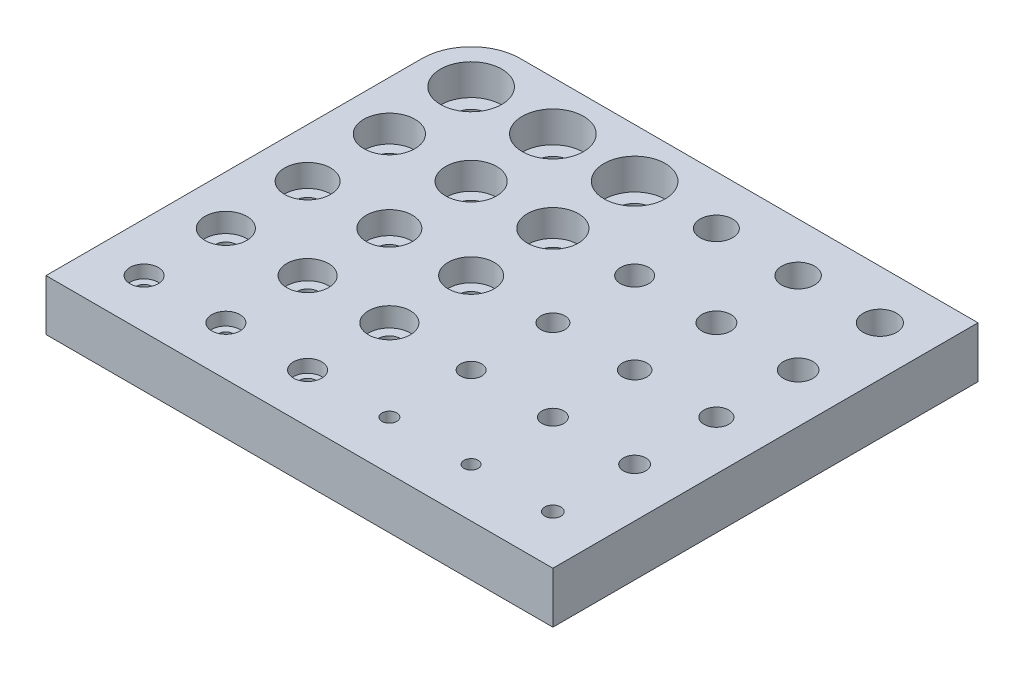
SolidWorks part; units mm, degrees
ref_plane "Front Plane" through (0, 0, 0) normal (0, 0, 1) x (1, 0, 0)
ref_plane "Top Plane" through (0, 0, 0) normal (0, 1, 0) x (1, 0, 0)
ref_plane "Right Plane" through (0, 0, 0) normal (1, 0, 0) x (0, 0, -1)
sketch "Sketch1" plane through (0, 0, 0) normal (0, 1, 0) x (1, 0, 0)
  line L0 (20.32, 7.62) -> (7.62, 7.62) construction
  line L1 (0, 0) -> (40.64, 0)
  line L2 (0, 0) -> (0, 66.04)
  line L3 (0, 66.04) -> (40.64, 66.04)
  line L4 (40.64, 0) -> (40.64, 66.04)
  line L5 (7.62, 7.62) -> (7.62, 20.32) construction
  line L6 (7.62, 7.62) -> (20.32, 7.62) construction
  circle A1 centre (20.32, 58.42) radius 2.5527
  circle A2 centre (33.02, 58.42) radius 2.5908
  circle A5 centre (33.02, 45.72) radius 2.286
  circle A6 centre (20.32, 45.72) radius 2.2479
  circle A9 centre (20.32, 33.02) radius 1.8987
  circle A10 centre (33.02, 33.02) radius 1.9304
  circle A13 centre (33.02, 20.32) radius 1.75
  circle A14 centre (20.32, 20.32) radius 1.7
  circle A16 centre (20.32, 7.62) radius 1.1
  circle A18 centre (33.02, 7.62) radius 1.25
  circle A20 centre (7.62, 58.42) radius 2.5273
  circle A21 centre (7.62, 45.72) radius 2.1971
  circle A22 centre (7.62, 33.02) radius 1.8669
  circle A23 centre (7.62, 7.62) radius 1.15
  circle A24 centre (7.62, 20.32) radius 1.65
  point P4 (7.62, 7.62)
  point P7 (20.32, 7.62)
  point P9 (33.02, 7.62)
  point P11 (20.32, 20.32)
  point P12 (33.02, 20.32)
  point P14 (20.32, 33.02)
  point P15 (33.02, 33.02)
  point P17 (20.32, 45.72)
  point P18 (33.02, 45.72)
  point P20 (20.32, 58.42)
  point P21 (33.02, 58.42)
  point P23 (7.62, 20.32)
  point P24 (7.62, 33.02)
  point P25 (7.62, 45.72)
  point P26 (7.62, 58.42)
  point P65 (7.6185, 7.62)
  dimension "D8" = 5.1054
  dimension "D9" = 5.1816
  dimension "D11" = 4.572
  dimension "D13" = 4.4958
  dimension "D14" = 3.7973
  dimension "D15" = 3.8608
  dimension "D17" = 3.4
  dimension "D18" = 3.5
  dimension "D20" = 2.2
  dimension "D21" = 2.5
  dimension "D23" = 5.0546
  dimension "D24" = 3.3
  dimension "D25" = 2.3
  dimension "D26" = 3.7338
  dimension "D27" = 4.3942
  dimension "D1" = 3
  dimension "D2" = 5
  dimension "D3" = 7.62
  dimension "D4" = 7.62
  dimension "D5" = 7.62
  dimension "D6" = 7.62
  dimension "D7" = 12.7
extrude "Boss-Extrude1" add sketch "Sketch1" against normal blind 7.9375
pattern_linear "LPattern1" count 2 spacing 38.1 along (1, 0, 0) of bodies 101
combine bodies "Combine1" operation type add bodies to combine 107 101
hole_wizard "CBORE for #10 Socket Head Cap Screw1" positions "Sketch2" profile "Sketch3" counterbore size "#10" standard "ANSI Inch" end condition through all
sketch "Sketch2" plane through (0, 0, 0) normal (0, 1, 0) x (1, 0, 0)
  point P0 (7.62, 58.42)
  point P4 (20.32, 58.42)
  point P7 (33.02, 58.42)
sketch "Sketch3" plane through (7.62, 0, -58.42) normal (1, 0, 0) x (0, 0, 1)
  line L0 (0, 0) -> (0, 7.9375)
  line L1 (0, 7.9375) -> (2.4892, 7.9375)
  line L3 (2.4892, 7.9375) -> (2.4892, 4.826)
  line L4 (2.4892, 4.826) -> (4.7625, 4.826)
  line L5 (4.7625, 4.826) -> (4.7625, 0)
  line L7 (4.7625, 0) -> (0, 0)
  line L11 (0, -6.35) -> (0, 107.95) construction
  dimension "Thru Hole Dia." = 4.9784
  dimension "Thru Hole Depth" = 7.9375
  dimension "C'Bore Dia." = 9.525
  dimension "C'Bore Depth" = 4.826
hole_wizard "CBORE for #8 Socket Head Cap Screw1" positions "Sketch4" profile "Sketch5" counterbore size "#8" standard "ANSI Inch" end condition through all
sketch "Sketch4" plane through (0, 0, 0) normal (0, 1, 0) x (1, 0, 0)
  point P0 (7.62, 45.72)
  point P3 (20.32, 45.72)
  point P6 (33.02, 45.72)
sketch "Sketch5" plane through (7.62, 0, -45.72) normal (1, 0, 0) x (0, 0, 1)
  line L0 (0, 0) -> (0, 7.9375)
  line L1 (0, 7.9375) -> (2.1526, 7.9375)
  line L3 (2.1526, 7.9375) -> (2.1526, 4.1656)
  line L4 (2.1526, 4.1656) -> (3.9687, 4.1656)
  line L5 (3.9687, 4.1656) -> (3.9687, 0)
  line L7 (3.9687, 0) -> (0, 0)
  line L11 (0, -6.35) -> (0, 107.95) construction
  dimension "Thru Hole Dia." = 4.3053
  dimension "Thru Hole Depth" = 7.9375
  dimension "C'Bore Dia." = 7.9375
  dimension "C'Bore Depth" = 4.1656
hole_wizard "CBORE for #6 Socket Head Cap Screw1" positions "Sketch6" profile "Sketch7" counterbore size "#6" standard "ANSI Inch" end condition through all
sketch "Sketch6" plane through (0, 0, 0) normal (0, 1, 0) x (1, 0, 0)
  point P0 (7.62, 33.02)
  point P3 (20.32, 33.02)
  point P6 (33.02, 33.02)
sketch "Sketch7" plane through (7.62, 0, -33.02) normal (1, 0, 0) x (0, 0, 1)
  line L0 (0, 0) -> (0, 7.9375)
  line L1 (0, 7.9375) -> (1.8288, 7.9375)
  line L3 (1.8288, 7.9375) -> (1.8288, 3.5052)
  line L4 (1.8288, 3.5052) -> (3.5725, 3.5052)
  line L5 (3.5725, 3.5052) -> (3.5725, 0)
  line L7 (3.5725, 0) -> (0, 0)
  line L11 (0, -6.35) -> (0, 107.95) construction
  dimension "Thru Hole Dia." = 3.6576
  dimension "Thru Hole Depth" = 7.9375
  dimension "C'Bore Dia." = 7.145
  dimension "C'Bore Depth" = 3.5052
hole_wizard "CBORE for M3 SHCS1" positions "Sketch8" profile "Sketch9" counterbore size "M3" standard "ANSI Metric" end condition through all
sketch "Sketch8" plane through (0, 0, 0) normal (0, 1, 0) x (1, 0, 0)
  point P0 (7.62, 20.32)
  point P3 (20.32, 20.32)
  point P6 (33.02, 20.32)
  point P12 (0, 0)
sketch "Sketch9" plane through (7.62, 0, -20.32) normal (1, 0, 0) x (0, 0, 1)
  line L0 (0, 0) -> (0, 7.9375)
  line L1 (0, 7.9375) -> (1.6, 7.9375)
  line L3 (1.6, 7.9375) -> (1.6, 3)
  line L4 (1.6, 3) -> (3.25, 3)
  line L5 (3.25, 3) -> (3.25, 0)
  line L7 (3.25, 0) -> (0, 0)
  line L11 (0, -6.35) -> (0, 107.95) construction
  dimension "Thru Hole Dia." = 3.2
  dimension "Thru Hole Depth" = 7.9375
  dimension "C'Bore Dia." = 6.5
  dimension "C'Bore Depth" = 3
hole_wizard "CBORE for M2 SHCS1" positions "Sketch10" profile "Sketch11" counterbore size "M2" standard "ANSI Metric" end condition through all
sketch "Sketch10" plane through (0, 0, 0) normal (0, 1, 0) x (1, 0, 0)
  point P0 (7.62, 7.62)
  point P3 (20.32, 7.62)
  point P6 (33.02, 7.62)
  point P12 (0, 0)
sketch "Sketch11" plane through (7.62, 0, -7.62) normal (1, 0, 0) x (0, 0, 1)
  line L0 (0, 0) -> (0, 7.9375)
  line L1 (0, 7.9375) -> (1.1, 7.9375)
  line L3 (1.1, 7.9375) -> (1.1, 2)
  line L4 (1.1, 2) -> (2.2, 2)
  line L5 (2.2, 2) -> (2.2, 0)
  line L7 (2.2, 0) -> (0, 0)
  line L11 (0, -6.35) -> (0, 107.95) construction
  dimension "Thru Hole Dia." = 2.2
  dimension "Thru Hole Depth" = 7.9375
  dimension "C'Bore Dia." = 4.4
  dimension "C'Bore Depth" = 2
fillet "Fillet1" radius 7.62 1 edges at (0, -3.9688, -66.04)
